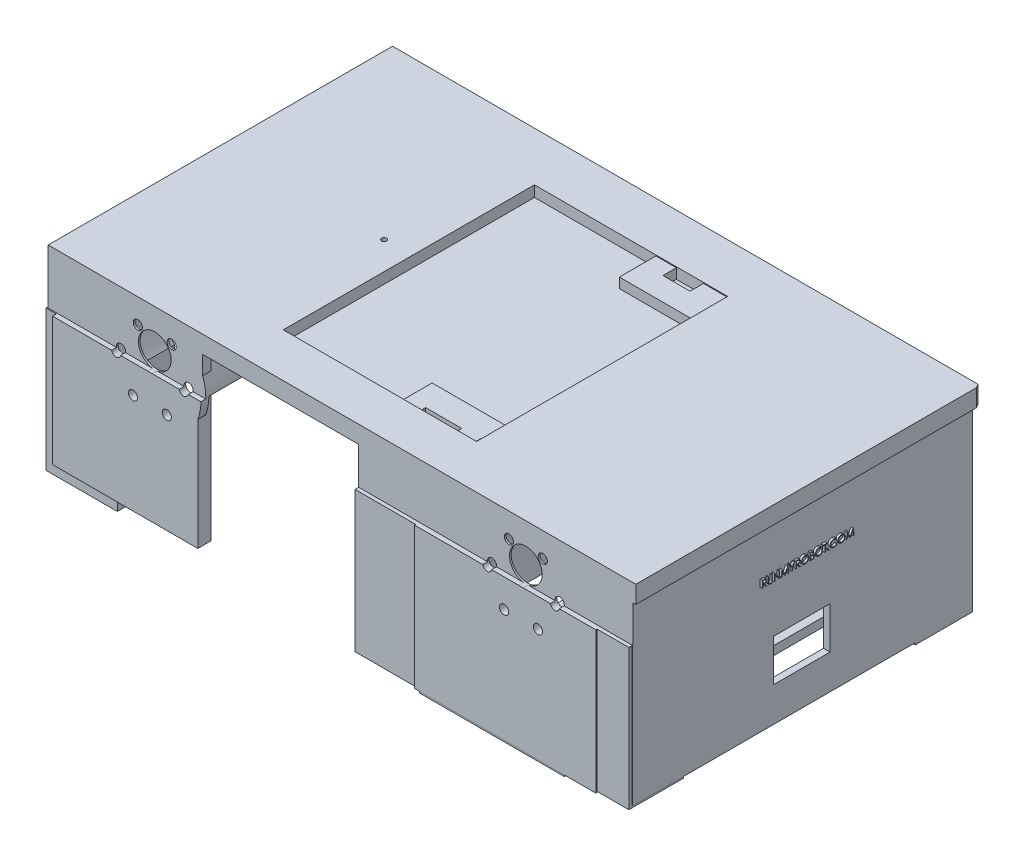
SolidWorks part; units mm, degrees
ref_plane "Front Plane" through (0, 0, 0) normal (0, 0, 1) x (1, 0, 0)
ref_plane "Top Plane" through (0, 0, 0) normal (0, 1, 0) x (1, 0, 0)
ref_plane "Right Plane" through (0, 0, 0) normal (1, 0, 0) x (0, 0, -1)
sketch "MotorHoldersSketch" plane through (0, 0, 0) normal (0, 0, 1) x (1, 0, 0)
  line L0 (0, 0) -> (170, 0) construction
  line L1 (0, 0) -> (0, 23.41) construction
  line L2 (170, 0) -> (170, 23.41) construction
  circle A0 centre (0, 0) radius 23.41
  circle A1 centre (170, 0) radius 23.41
ref_axis "MotorCenterAxis1" through (0, 0, 0) along (0, 0, 1)
ref_axis "MotorCenterAxis2" through (170, 0, 0) along (0, 0, 1)
extrude "MotorHolders" add sketch "MotorHoldersSketch" along normal blind 80 and the other way blind 80
sketch "Sketch3" plane through (0, 0, 0) normal (0, 0, 1) x (1, 0, 0)
  line L1 (1.9406, 21.133) -> (168.3435, 21.133)
  line L2 (1.9406, 21.133) -> (1.9406, 18.3155)
  line L3 (1.9406, 18.3155) -> (168.3435, 18.3155)
  line L4 (168.3435, 21.133) -> (168.3435, 18.3155)
sketch "Sketch4" plane through (0, 0, 0) normal (0, 1, 0) x (1, 0, 0)
  line L1 (221.2811, -76.3794) -> (-41.4939, -76.3794)
  line L2 (221.2811, -76.3794) -> (221.2811, 76.7331)
  line L3 (221.2811, 76.7331) -> (-41.4939, 76.7331)
  line L4 (-41.4939, -76.3794) -> (-41.4939, 76.7331)
extrude "Cut-Extrude1" cut sketch "Sketch4" against normal blind 26
ref_axis "Axis3" through (170, 0, 0) along (0, -1, 0)
sketch3d "ReferencePlanePosition"
  line L0 (170, 0, 0) -> (170, -34.8293, 0)
  line L1 (170, 0, 0) -> (170, -38.994, 0) construction
ref_plane "ReferencePlane" through (170, -34.8293, 0) normal (0, -1, 0) x (-1, 0, 0)
sketch "Sketch6" plane through (170, -34.8293, 0) normal (0, -1, 0) x (-1, 0, 0)
  line L1 (219.5858, 78.949) -> (145.1716, 78.949)
  line L2 (219.5858, 78.949) -> (219.5858, 65.5282)
  line L3 (219.5858, 65.5282) -> (145.1716, 65.5282)
  line L4 (145.1716, 78.949) -> (145.1716, 65.5282)
  line L5 (219.3147, -52.1095) -> (186.667, -52.1095)
  line L6 (219.3147, -52.1095) -> (219.3147, -78.2822)
  line L7 (219.3147, -78.2822) -> (186.667, -78.2822)
  line L8 (186.667, -52.1095) -> (186.667, -78.2822)
  line L9 (75.6651, 77.8627) -> (19.9904, 77.8627)
  line L10 (75.6651, 77.8627) -> (75.6651, 40.7512)
  line L11 (75.6651, 40.7512) -> (19.9904, 40.7512)
  line L12 (19.9904, 77.8627) -> (19.9904, 40.7512)
  line L13 (76.5596, -44.1716) -> (20.0852, -44.1716)
  line L14 (76.5596, -44.1716) -> (76.5596, -79.4437)
  line L15 (76.5596, -79.4437) -> (20.0852, -79.4437)
  line L16 (20.0852, -44.1716) -> (20.0852, -79.4437)
  line L17 (213.765, 73.0364) -> (192.9548, 73.0364)
  line L18 (213.765, 73.0364) -> (213.765, 71.0153)
  line L19 (213.765, 71.0153) -> (192.9548, 71.0153)
  line L20 (192.9548, 73.0364) -> (192.9548, 71.0153)
  line L21 (41.3552, 69.1777) -> (28.5109, 69.1777)
  line L22 (41.3552, 69.1777) -> (41.3552, 50.8413)
  line L23 (41.3552, 50.8413) -> (28.5109, 50.8413)
  line L24 (28.5109, 69.1777) -> (28.5109, 50.8413)
  line L25 (43.3068, -72.8101) -> (32.1723, -72.8101)
  line L26 (43.3068, -72.8101) -> (43.3068, -54.7747)
  line L27 (43.3068, -54.7747) -> (32.1723, -54.7747)
  line L28 (32.1723, -72.8101) -> (32.1723, -54.7747)
  line L29 (211.9411, -70.4881) -> (201.0982, -70.4881)
  line L30 (211.9411, -70.4881) -> (211.9411, -60.1404)
  line L31 (211.9411, -60.1404) -> (201.0982, -60.1404)
  line L32 (201.0982, -70.4881) -> (201.0982, -60.1404)
  line L37 (66.2772, 51.3198) -> (53.8697, 51.3198)
  line L38 (66.2772, 51.3198) -> (66.2772, 67.7632)
  line L39 (66.2772, 67.7632) -> (53.8697, 67.7632)
  line L40 (53.8697, 51.3198) -> (53.8697, 67.7632)
  line L45 (68.2481, -69.8638) -> (51.7107, -69.8638)
  line L46 (68.2481, -69.8638) -> (68.2481, -55.4273)
  line L47 (68.2481, -55.4273) -> (51.7107, -55.4273)
  line L48 (51.7107, -69.8638) -> (51.7107, -55.4273)
  line L49 (-20.7001, -79.4437) -> (-48.8506, -79.4437)
  line L50 (-20.7001, -79.4437) -> (-20.7001, -54.5097)
  line L51 (-20.7001, -54.5097) -> (-48.8506, -54.5097)
  line L52 (-48.8506, -79.4437) -> (-48.8506, -54.5097)
  line L53 (-18.3873, 77.8627) -> (-49.0581, 77.8627)
  line L54 (-18.3873, 77.8627) -> (-18.3873, 51.5325)
  line L55 (-18.3873, 51.5325) -> (-49.0581, 51.5325)
  line L56 (-49.0581, 77.8627) -> (-49.0581, 51.5325)
  line L57 (-41.8141, -72.8101) -> (-31.6362, -72.8101)
  line L58 (-41.8141, -72.8101) -> (-41.8141, -62.9794)
  line L59 (-41.8141, -62.9794) -> (-31.6362, -62.9794)
  line L60 (-31.6362, -72.8101) -> (-31.6362, -62.9794)
  line L61 (-31.6362, 69.1777) -> (-41.5347, 69.1777)
  line L62 (-31.6362, 69.1777) -> (-31.6362, 58.5421)
  line L63 (-31.6362, 58.5421) -> (-41.5347, 58.5421)
  line L64 (-41.5347, 69.1777) -> (-41.5347, 58.5421)
extrude "PowerBankHolders" add sketch "Sketch6" along normal blind 30 and the other way blind 59 separate body
sketch3d "3DSketch3"
  line L0 (170, 0, 0) -> (170, -64.5, 0) construction
ref_plane "Plane2" through (170, -64.5, 0) normal (0, -1, 0) x (-1, 0, 0)
sketch "Sketch7" plane through (170, -64.5, 0) normal (0, -1, 0) x (-1, 0, 0)
  line L1 (-9.5047, -80.801) -> (181.32, -80.801)
  line L2 (-9.5047, -80.801) -> (-9.5047, 73.8662)
  line L3 (-9.5047, 73.8662) -> (181.32, 73.8662)
  line L4 (181.32, -80.801) -> (181.32, 73.8662)
  line L5 (151.8712, -54.3972) -> (26.5361, -54.3972)
  line L6 (151.8712, -54.3972) -> (151.8712, 46.2413)
  line L7 (151.8712, 46.2413) -> (26.5361, 46.2413)
  line L8 (26.5361, -54.3972) -> (26.5361, 46.2413)
ref_point "Point1"
ref_point "Point2"
sketch3d "3DSketch11"
  line L0 (0, 0, -80) -> (170, 0, 80) construction
  point P4 (85, 0, 0)
sketch "MotorHolderExtrudeSketch" plane through (0, 0, 0) normal (0, 0, 1) x (1, 0, 0)
  circle A0 centre (170, 0) radius 20.415
  circle A1 centre (0, 0) radius 20.415
  circle A3 centre (0, 0) radius 23.41 construction
  circle A4 centre (170, 0) radius 23.41 construction
ref_point "TopOfMotors"
ref_plane "TangentToTopOfMotors" through (0, -20.415, 0) normal (0, 1, 0) x (1, 0, 0)
ref_axis "Axis4" through (85, 0, 0) along (0, -1, 0)
ref_plane "BottomOfPowerBankRegion" through (0, -20.425, 0) normal (0, 1, 0) x (1, 0, 0)
sketch "Sketch11" plane through (0, -20.425, 0) normal (0, 1, 0) x (1, 0, 0)
  line L0 (-18.9327, 3.7419) -> (188.9327, -3.7419) construction
  line L5 (-18.9327, -64.7581) -> (-18.9327, 72.2419)
  line L6 (188.9327, 63.7581) -> (188.9327, -71.2419)
  line L7 (188.9327, -71.2419) -> (-18.9327, -64.7581)
  line L8 (188.9327, 63.7581) -> (-18.9327, 72.2419)
  circle A0 centre (85, 0) radius 104 construction
ref_point "CenterAtBottomOfPowerBank"
ref_plane "TopOfPowerBankPlane" through (0, -54.425, 0) normal (0, 1, 0) x (1, 0, 0)
sketch "Sketch13" plane through (0, -54.425, 0) normal (0, 1, 0) x (1, 0, 0)
  line L1 (-19.4498, 72.5454) -> (166.1636, 72.5454)
  line L2 (-19.4498, 72.5454) -> (-19.4498, -78.2051)
  line L3 (-19.4498, -78.2051) -> (166.1636, -78.2051)
  line L4 (166.1636, 72.5454) -> (166.1636, -78.2051)
  line L5 (19.3173, -49.583) -> (137.9607, -49.583)
  line L6 (19.3173, -49.583) -> (19.3173, -21.0549)
  line L7 (19.3173, -21.0549) -> (137.9607, -21.0549)
  line L8 (137.9607, -49.583) -> (137.9607, -21.0549)
  line L9 (19.3173, 56.6778) -> (137.9607, 56.6778)
  line L10 (19.3173, 56.6778) -> (19.3173, 36.3234)
  line L11 (19.3173, 36.3234) -> (137.9607, 36.3234)
  line L12 (137.9607, 56.6778) -> (137.9607, 36.3234)
  line L13 (19.3173, 18.3186) -> (137.9607, 18.3186)
  line L14 (19.3173, 18.3186) -> (19.3173, -7.3615)
  line L15 (19.3173, -7.3615) -> (137.9607, -7.3615)
  line L16 (137.9607, 18.3186) -> (137.9607, -7.3615)
sketch "Sketch15" plane through (150.0096, 0, 0) normal (1, 0, 0) x (0, 0, -1)
  line L1 (72.5313, -25.7765) -> (45.7099, -25.7765)
  line L2 (72.5313, -25.7765) -> (72.5313, -24.2242)
  line L3 (72.5313, -24.2242) -> (45.7099, -24.2242)
  line L4 (45.7099, -25.7765) -> (45.7099, -24.2242)
extrude "PowerBankCut" cut sketch "Sketch11" against normal blind 64
ref_plane "Plane6" through (0, 0, 0) normal (0, 0, 1) x (1, 0, 0)
sketch "MotorGeometry1" plane through (0, 0, 0) normal (0, 0, 1) x (1, 0, 0)
  line L0 (170, 0) -> (170, -13.42)
  line L1 (170, 0) -> (170, -34.8293) construction
  line L2 (170, -13.42) -> (162.25, -13.42) construction
  line L3 (170, -13.42) -> (177.75, -13.42) construction
  line L4 (170, -13.42) -> (170, 7) construction
  line L5 (170, 0) -> (185.5, 0) construction
  line L6 (170, 0) -> (154.5, 0) construction
  line L7 (170, 0) -> (170, 13.42) construction
  line L8 (170, 0) -> (170, 23.41) construction
  line L9 (170, 13.42) -> (177.75, 13.42) construction
  line L10 (170, 13.42) -> (162.25, 13.42)
ref_axis "BoltAxisA" through (185.5, 0, 0) along (0, 0, 1)
ref_axis "BoltAxisB" through (177.75, -13.42, 0) along (0, 0, 1)
ref_axis "BoltAxisC" through (162.25, -13.42, 0) along (0, 0, 1)
ref_axis "BoltAxisD" through (154.5, 0, 0) along (0, 0, 1)
ref_axis "BoltAxisE" through (162.25, 13.42, 0) along (0, 0, 1)
ref_axis "BoltAxisF" through (177.75, 13.42, 0) along (0, 0, 1)
ref_point "Point6"
ref_point "Point7"
ref_point "Point8"
ref_point "Point9"
ref_point "Point10"
ref_point "Point11"
ref_point "Point12"
ref_point "Point13"
ref_point "Point14"
ref_point "Point15"
ref_point "Point16"
ref_point "Point17"
ref_plane "Plane7" through (0, 0, 0) normal (0, 0, 1) x (1, 0, 0)
sketch "MotorGeometry2" plane through (0, 0, 0) normal (0, 0, 1) x (1, 0, 0)
  line L0 (0, 0) -> (0, -13.42) construction
  line L1 (0, -13.42) -> (7.75, -13.42) construction
  line L2 (0, -13.42) -> (-7.75, -13.42) construction
  line L3 (0, 0) -> (0, 13.42)
  line L4 (0, -13.42) -> (0, 7) construction
  line L5 (0, 13.42) -> (7.75, 13.42) construction
  line L6 (0, 13.42) -> (-7.75, 13.42) construction
  line L7 (0, 0) -> (15.5, 0) construction
  line L8 (0, 0) -> (-15.5, 0) construction
  line L9 (0, 0) -> (0, 23.41) construction
ref_axis "Axis11" through (15.5, 0, 0) along (0, 0, 1)
ref_axis "Axis12" through (7.75, 13.42, 0) along (0, 0, 1)
ref_axis "Axis13" through (-7.75, 13.42, 0) along (0, 0, 1)
ref_axis "Axis14" through (-15.5, 0, 0) along (0, 0, 1)
ref_axis "Axis15" through (-7.75, -13.42, 0) along (0, 0, 1)
ref_axis "Axis16" through (7.75, -13.42, 0) along (0, 0, 1)
ref_point "Point18"
ref_point "Point19"
ref_point "Point20"
ref_point "Point21"
ref_point "Point22"
ref_point "Point23"
ref_point "Point24"
ref_point "Point25"
ref_point "Point26"
ref_point "Point27"
ref_point "Point28"
ref_point "Point29"
ref_plane "BottomPlane" through (0, 19.575, 0) normal (0, 1, 0) x (1, 0, 0)
ref_axis "OutputShaftReference1" through (0, 7, 0) along (0, 0, 1)
ref_point "Point35"
ref_axis "OutputShaftReference2" through (170, 7, 0) along (0, 0, 1)
sketch "Sketch21" plane through (0, 19.575, 0) normal (0, 1, 0) x (1, 0, 0)
  line L0 (219.6842, -79.5488) -> (-50.341, -79.5488) construction
  line L1 (-50.341, -79.5488) -> (-50.341, 79.7899) construction
  line L2 (-50.341, 79.7899) -> (219.6842, 79.7899) construction
  line L3 (219.6842, 79.7899) -> (219.6842, -79.5488) construction
  line L4 (127.2472, -57.5918) -> (127.2472, 57.4773)
  line L5 (127.2472, 57.4773) -> (38.7099, 57.4773)
  line L6 (38.7099, 57.4773) -> (38.7099, -57.5918)
  line L7 (38.7099, -57.5918) -> (127.2472, -57.5918)
  circle A0 centre (85, 0) radius 156.3953
extrude "BottomPlate" add sketch "Sketch21" along normal blind 5 and the other way blind 3
ref_plane "HoleReferencePlane1" through (0, 0, 80) normal (0, 0, 1) x (1, 0, 0)
ref_point "OutputShaftPosition3"
ref_point "OutputShaftPosition1"
sketch "Sketch23" plane through (0, 0, 80) normal (0, 0, 1) x (1, 0, 0)
  line L1 (21.9586, -59.3229) -> (-44.5901, -59.3229)
  line L2 (21.9586, -59.3229) -> (21.9586, 21.8402)
  line L3 (21.9586, 21.8402) -> (-44.5901, 21.8402)
  line L4 (-44.5901, -59.3229) -> (-44.5901, 21.8402)
  line L5 (121.3218, 21.8402) -> (204.258, 21.8402)
  line L6 (121.3218, 21.8402) -> (121.3218, -65.2231)
  line L7 (121.3218, -65.2231) -> (204.258, -65.2231)
  line L8 (204.258, 21.8402) -> (204.258, -65.2231)
extrude "MotorMountingSupport1" add sketch "Sketch23" against normal blind 6
ref_plane "HoleReferencePlane2" through (0, 0, -80) normal (0, 0, -1) x (-1, 0, 0)
ref_point "OutputShaftPosition4"
ref_point "OutputShaftPosition2"
sketch "Sketch24" plane through (0, 0, -80) normal (0, 0, -1) x (-1, 0, 0)
  line L1 (-202.1905, -67.1257) -> (-139.5471, -67.1257)
  line L2 (-202.1905, -67.1257) -> (-202.1905, 19.2374)
  line L3 (-202.1905, 19.2374) -> (-139.5471, 19.2374)
  line L4 (-139.5471, -67.1257) -> (-139.5471, 19.2374)
  line L5 (-24.3642, -64.1521) -> (29.5505, -64.1521)
  line L6 (-24.3642, -64.1521) -> (-24.3642, 22.5226)
  line L7 (-24.3642, 22.5226) -> (29.5505, 22.5226)
  line L8 (29.5505, -64.1521) -> (29.5505, 22.5226)
extrude "MotorMountingSuppor2" add sketch "Sketch24" against normal blind 6
sketch "Sketch17" plane through (0, 0, 80) normal (0, 0, 1) x (1, 0, 0)
  circle A0 centre (185.5, 0) radius 2.1
  circle A1 centre (177.75, -13.42) radius 2.1
  circle A2 centre (162.25, -13.42) radius 2.1
  circle A3 centre (154.5, 0) radius 2.1
  circle A4 centre (162.25, 13.42) radius 2.1
  circle A5 centre (177.75, 13.42) radius 2.1
  circle A6 centre (170, 7) radius 7.5
extrude "MotorHoles1" cut sketch "Sketch17" against normal blind 31.5
sketch "Sketch19" plane through (0, 0, -80) normal (0, 0, -1) x (-1, 0, 0)
  circle A0 centre (-185.5, 0) radius 2.1
  circle A1 centre (-177.75, -13.42) radius 2.1
  circle A2 centre (-162.25, -13.42) radius 2.1
  circle A3 centre (-154.5, 0) radius 2.1
  circle A4 centre (-162.25, 13.42) radius 2.1
  circle A5 centre (-177.75, 13.42) radius 2.1
  circle A6 centre (-170, 7) radius 7.5
sketch "BoltHolesSketch3" plane through (0, 0, 80) normal (0, 0, 1) x (1, 0, 0)
  circle A0 centre (7.75, -13.42) radius 2.1
  circle A1 centre (15.5, 0) radius 2.1
  circle A2 centre (7.75, 13.42) radius 2.1
  circle A3 centre (-7.75, 13.42) radius 2.1
  circle A4 centre (-15.5, 0) radius 2.1
  circle A5 centre (-7.75, -13.42) radius 2.1
  circle A6 centre (0, 7) radius 7.5
extrude "Cut-Extrude4" cut sketch "Sketch19" against normal blind 30
extrude "MotorHoles3" cut sketch "BoltHolesSketch3" against normal blind 31.5
sketch "BoltHolesSketch4" plane through (0, 0, -80) normal (0, 0, -1) x (-1, 0, 0)
  circle A0 centre (-15.5, 0) radius 2.1
  circle A1 centre (-7.75, 13.42) radius 2.1
  circle A2 centre (7.75, 13.42) radius 2.1
  circle A3 centre (15.5, 0) radius 2.1
  circle A4 centre (7.75, -13.42) radius 2.1
  circle A5 centre (-7.75, -13.42) radius 2.1
  circle A6 centre (0, 7) radius 7.5
extrude "MotorHoles4" cut sketch "BoltHolesSketch4" against normal blind 15
ref_plane "Front" through (219.0581, 0, 0) normal (1, 0, 0) x (0, 0, -1)
sketch "Sketch29" plane through (219.0581, 0, 0) normal (1, 0, 0) x (0, 0, -1)
  line L1 (76.6955, -63.9254) -> (-77.9397, -63.9254)
  line L2 (76.6955, -63.9254) -> (76.6955, 20.2062)
  line L3 (76.6955, 20.2062) -> (-77.9397, 20.2062)
  line L4 (-77.9397, -63.9254) -> (-77.9397, 20.2062)
  line L5 (-13.4507, -48.1531) -> (12.5493, -48.1531)
  line L6 (-13.4507, -48.1531) -> (-13.4507, -28.9404)
  line L7 (-13.4507, -28.9404) -> (12.5493, -28.9404)
  line L8 (12.5493, -48.1531) -> (12.5493, -28.9404)
extrude "Boss-Extrude8" add sketch "Sketch29" against normal blind 3
ref_plane "RaspberryPiBasePlane" through (0, 16.575, 0) normal (0, -1, 0) x (-1, 0, 0)
sketch "Sketch27" plane through (0, 16.575, 0) normal (0, -1, 0) x (-1, 0, 0)
  line L1 (31.6337, 64.5517) -> (-194.8264, 64.5517)
  line L2 (31.6337, 64.5517) -> (31.6337, -65.4335)
  line L3 (31.6337, -65.4335) -> (-194.8264, -65.4335)
  line L4 (-194.8264, 64.5517) -> (-194.8264, -65.4335)
extrude "Boss-Extrude6" add sketch "Sketch27" against normal blind 3
ref_plane "Plane12" through (0, -64.8293, 0) normal (0, -1, 0) x (-1, 0, 0)
sketch "Sketch28" plane through (0, -64.8293, 0) normal (0, -1, 0) x (-1, 0, 0)
  line L1 (-189.3897, -79.549) -> (-123.0026, -79.549)
  line L2 (-189.3897, -79.549) -> (-189.3897, 78.1499)
  line L3 (-189.3897, 78.1499) -> (-123.0026, 78.1499)
  line L4 (-123.0026, -79.549) -> (-123.0026, 78.1499)
extrude "Boss-Extrude7" add sketch "Sketch28" along normal blind 1.5 and the other way blind 2.5
extrude "MotorHolderCut" cut sketch "MotorHolderExtrudeSketch" against normal blind 77 and the other way blind 77
sketch "Sketch31" plane through (219.0581, 0, 0) normal (1, 0, 0) x (0, 0, -1)
  text T0 "RUNMYROBOT.COM"
extrude "Boss-Extrude9" add sketch "Sketch31" along normal blind 1
sketch "Sketch32" plane through (0, 19.575, 0) normal (0, 1, 0) x (1, 0, 0)
  line L1 (-48.8137, 79.9559) -> (220.392, 79.9559)
  line L2 (-48.8137, 79.9559) -> (-48.8137, -77.7711)
  line L3 (-48.8137, -77.7711) -> (220.392, -77.7711)
  line L4 (220.392, 79.9559) -> (220.392, -77.7711)
  line L5 (283.5566, -218.7268) -> (-136.4889, -218.7268)
  line L8 (-136.4889, -218.7268) -> (-136.4889, 206.3198)
  line L10 (283.5566, 206.3198) -> (283.5566, -218.7268)
  line L13 (283.5566, 206.3198) -> (-136.4889, 206.3198)
extrude "Cut-Extrude5" cut sketch "Sketch32" along normal blind 20 and the other way blind 20
sketch "Sketch35" plane through (0, 0, -79.9559) normal (0, 0, -1) x (-1, 0, 0)
  line L0 (69.0502, 16.3777) -> (-36.4474, 27.6206)
  line L1 (-36.4474, 27.6206) -> (71.6404, 26.1593)
  line L2 (69.0502, 16.3777) -> (71.6404, 26.1593)
  line L3 (-223.8844, 30.8145) -> (-223.8844, 17.5678)
  line L4 (-223.8844, 17.5678) -> (-116.0163, 30.8145)
  line L5 (-116.0163, 30.8145) -> (-223.8844, 30.8145)
sketch "Sketch36" plane through (-49.3147, 0, 0) normal (-1, 0, 0) x (0, 0, 1)
  line L0 (52.1095, -64.8293) -> (52.1095, -39.2093) construction
  line L1 (52.1095, -0.425) -> (52.1095, -64.8293) construction
  line L2 (52.1095, -39.2093) -> (52.1095, -64.8293) construction
  circle A0 centre (52.1095, -39.2093) radius 7.4588
extrude "Cut-Extrude6" cut sketch "Sketch36" against normal blind 40
sketch "Sketch37" plane through (0, -20.425, 0) normal (0, -1, 0) x (1, 0, 0)
  line L1 (144.416, -35.6729) -> (89.0759, -35.6729)
  line L2 (144.416, -35.6729) -> (144.416, -65.4438)
  line L3 (144.416, -65.4438) -> (89.0759, -65.4438)
  line L4 (89.0759, -35.6729) -> (89.0759, -65.4438)
extrude "Cut-Extrude7" cut sketch "Sketch37" against normal blind 36
sketch "Sketch38" plane through (0, 16.575, 0) normal (0, -1, 0) x (1, 0, 0)
  line L0 (25.9964, 77.7711) -> (25.9964, -1.3165) construction
  line L1 (-48.8137, 77.7711) -> (220.6877, 77.7711) construction
  circle A0 centre (25.9964, -1.3165) radius 1.1452
extrude "Cut-Extrude8" cut sketch "Sketch38" against normal blind 10
